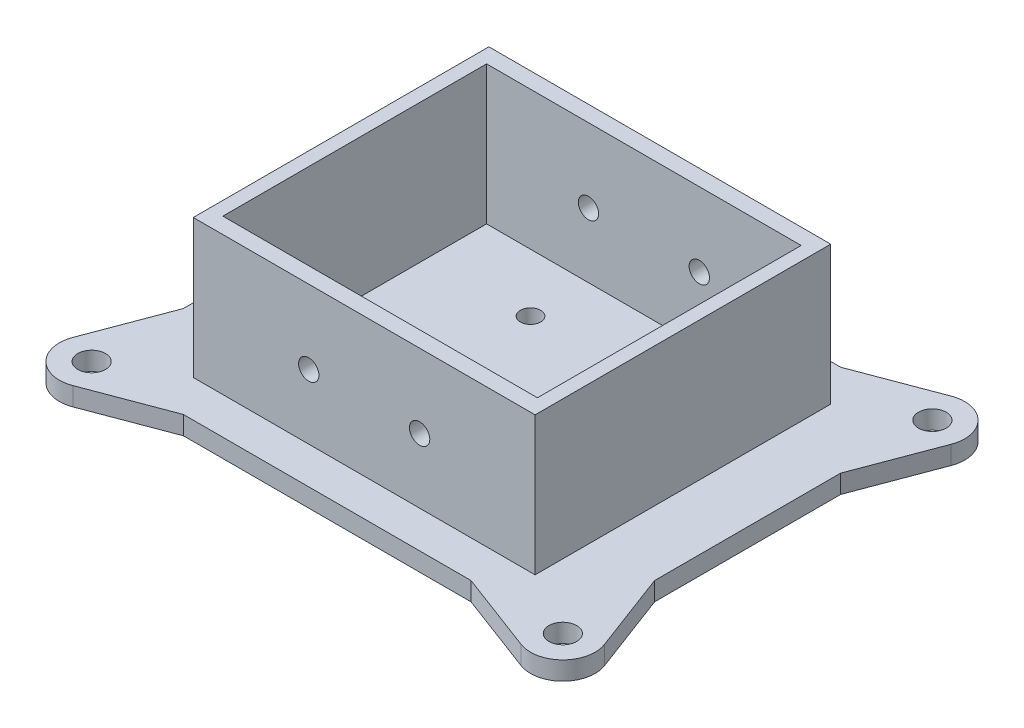
SolidWorks part; units mm, degrees
ref_plane "前视基准面" through (0, 0, 0) normal (0, 0, 1) x (1, 0, 0)
ref_plane "上视基准面" through (0, 0, 0) normal (0, 1, 0) x (1, 0, 0)
ref_plane "右视基准面" through (0, 0, 0) normal (1, 0, 0) x (0, 0, -1)
other "Configuration Table"
sketch "Sketch1" plane through (0, 0, 0) normal (0, 1, 0) x (1, 0, 0)
  line L0 (-24.2665, 23.2754) -> (-15.5689, 20)
  line L10 (24.2665, 23.2754) -> (15.5689, 20)
  line L11 (24.2665, -23.2754) -> (15.5689, -20)
  line L12 (-24.2665, -23.2754) -> (-15.5689, -20)
  line L13 (-28.7754, 18.7665) -> (-25.5, 10.0689)
  line L14 (28.7754, 18.7665) -> (25.5, 10.0689)
  line L15 (28.7754, -18.7665) -> (25.5, -10.0689)
  line L16 (-28.7754, -18.7665) -> (-25.5, -10.0689)
  line L17 (-25.5, 10.0689) -> (-25.5, -10.0689)
  line L18 (-15.5689, 20) -> (15.5689, 20)
  line L20 (25.5, 10.0689) -> (25.5, -10.0689)
  line L24 (-15.5689, -20) -> (15.5689, -20)
  circle A0 centre (-25.5, 20) radius 1.5
  circle A1 centre (25.5, 20) radius 1.5
  circle A2 centre (25.5, -20) radius 1.5
  circle A3 centre (-25.5, -20) radius 1.5
  arc A4 (-24.2665, 23.2754) -> (-28.7754, 18.7665) centre (-25.5, 20) ccw
  arc A5 (28.7754, 18.7665) -> (24.2665, 23.2754) centre (25.5, 20) ccw
  arc A6 (24.2665, -23.2754) -> (28.7754, -18.7665) centre (25.5, -20) ccw
  arc A7 (-28.7754, -18.7665) -> (-24.2665, -23.2754) centre (-25.5, -20) ccw
  point P0 (0, 0)
  dimension "D1" = 40
  dimension "D2" = 51
extrude "Boss-Extrude2" add sketch "Sketch1" along normal blind 2
sketch "Sketch2" plane through (0, 2, 0) normal (0, 1, 0) x (1, 0, 0)
  line L1 (-17.025, 14.275) -> (17.025, 14.275)
  line L2 (-17.025, 14.275) -> (-17.025, -14.275)
  line L3 (-17.025, -14.275) -> (17.025, -14.275)
  line L4 (17.025, 14.275) -> (17.025, -14.275)
  line L5 (0, -14.275) -> (0, 14.275) construction
  line L6 (-17.025, 0) -> (17.025, 0) construction
  line L7 (-18.5, 16) -> (18.5, 16)
  line L8 (-18.5, 16) -> (-18.5, -16)
  line L9 (-18.5, -16) -> (18.5, -16)
  line L10 (18.5, 16) -> (18.5, -16)
  line L11 (0, -16) -> (0, 16) construction
  line L12 (-18.5, 0) -> (18.5, 0) construction
  line L13 (-6, 8) -> (6, 8)
  line L14 (-6, 8) -> (-6, -8)
  line L15 (-6, -8) -> (6, -8)
  line L16 (6, 8) -> (6, -8)
  line L17 (0, -8) -> (0, 8) construction
  line L18 (-6, 0) -> (6, 0) construction
  circle A0 centre (-6, 8) radius 1.1
  circle A1 centre (6, 8) radius 1.1
  circle A2 centre (6, -8) radius 1.1
  circle A3 centre (-6, -8) radius 1.1
  point P0 (0, 0)
  point P4 (0, 0)
  point P11 (0, 0)
  dimension "D1" = 28.55
  dimension "D2" = 34.05
  dimension "D3" = 32
  dimension "D4" = 37
  dimension "D5" = 16
  dimension "D6" = 12
extrude "Boss-Extrude3" add sketch "Sketch2" along normal blind 15 contours L10 L7 L8 L9 L1 L4 L3 L2 region at (0, 2, -15.5108)
sketch "Sketch3" plane through (0, 0, -14.275) normal (0, 0, 1) x (1, 0, 0)
  line L0 (-17.025, 2) -> (17.025, 2) construction
  line L1 (-6, -5) -> (6, -5)
  line L2 (-6, -5) -> (-6, 9)
  line L3 (-6, 9) -> (6, 9)
  line L4 (6, -5) -> (6, 9)
  line L5 (0, 9) -> (0, -5) construction
  line L6 (-6, 2) -> (6, 2) construction
  circle A0 centre (-6, 9) radius 1.1
  circle A1 centre (6, 9) radius 1.1
  point P0 (0, 2)
  dimension "D1" = 14
  dimension "D2" = 12
extrude "Cut-Extrude1" cut sketch "Sketch3" against normal blind 11 and the other way blind 40 contours L3 A0 L2 | L2 A0 L3 | L4 A1 L3 | L3 A1 L4 region at (-6.1556, 9.1556, -14.275) region at (-5.5331, 8.5331, -14.275) region at (5.5331, 8.5331, -14.275) region at (6.1556, 9.1556, -14.275)
extrude "Cut-Extrude2" cut sketch "Sketch2<4>" against normal blind 11 contours A0 | A1 | A2 | A3
sketch "Sketch2<4>" plane through (0, 2, 0) normal (0, 1, 0) x (1, 0, 0) same geometry as "Sketch2"
